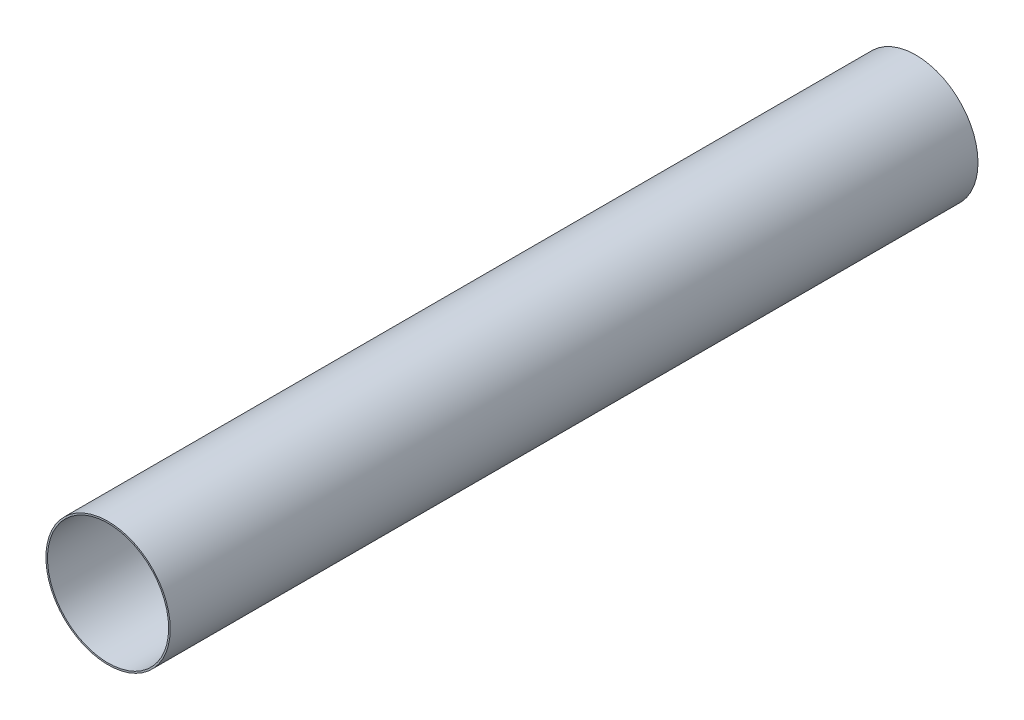
SolidWorks part; units mm, degrees
material "Thornel Mat VMA"
ref_plane "Front Plane" through (0, 0, 0) normal (0, 0, 1) x (1, 0, 0)
ref_plane "Top Plane" through (0, 0, 0) normal (0, 1, 0) x (1, 0, 0)
ref_plane "Right Plane" through (0, 0, 0) normal (1, 0, 0) x (0, 0, -1)
sketch "Sketch1" plane through (0, 0, 0) normal (0, 0, 1) x (1, 0, 0)
  circle A0 centre (0, 0) radius 78.2
  circle A1 centre (0, 0) radius 76.2
  dimension "D1" = 152.4
  dimension "D2" = 156.4
extrude "Boss-Extrude1" add sketch "Sketch1" along normal mid plane 1016
equation "\"TubeDiameter\"= 6.000in"
equation "\"D1@Sketch1\"=\"TubeDiameter\""
equation "\"D2@Sketch1\"=\"TubeDiameter\"+4mm"
